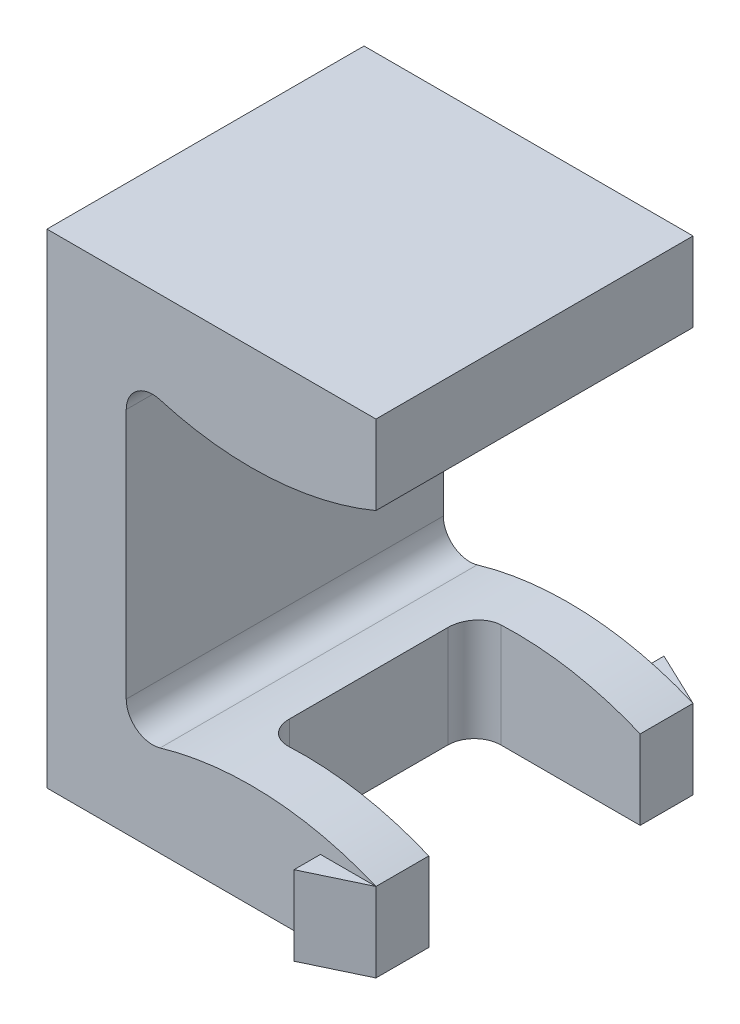
SolidWorks part; units mm, degrees
ref_plane "Front Plane" through (0, 0, 0) normal (0, 0, 1) x (1, 0, 0)
ref_plane "Top Plane" through (0, 0, 0) normal (0, 1, 0) x (1, 0, 0)
ref_plane "Right Plane" through (0, 0, 0) normal (1, 0, 0) x (0, 0, -1)
sketch "Sketch1" plane through (0, 0, 0) normal (0, 0, 1) x (1, 0, 0)
  line L2 (-159.7982, 9.1594) -> (-172.2482, 9.1594)
  line L3 (-172.2482, 9.1594) -> (-172.2482, -9.1594)
  line L7 (-169.2482, -22.8519) -> (-169.2482, 6.1594) construction
  line L12 (-169.2482, 5.1594) -> (-169.2482, 1.9844) construction
  line L13 (-142.8048, 5.1594) -> (-142.8048, -5.1594) construction
  line L15 (-156.5482, 5.1594) -> (21.2518, 5.1594) construction
  line L16 (-156.5482, -5.1594) -> (21.2518, -5.1594) construction
  line L23 (-159.7982, 6.1594) -> (-159.7982, 9.1594)
  line L28 (-164.5232, 5.2094) -> (-144.5007, 5.2094) construction
  line L29 (-156.5482, 5.1594) -> (-169.2482, 5.1594) construction
  line L30 (-169.2482, 6.1594) -> (-169.2482, 5.1594)
  line L34 (-169.2482, 5.1594) -> (-169.2482, -5.1594)
  line L35 (-172.2482, 0) -> (-169.2482, 0) construction
  line L36 (-169.2482, -6.1594) -> (-169.2482, -5.1594)
  line L37 (-159.7982, -6.1594) -> (-159.7982, -9.1594)
  line L38 (-159.7982, -9.1594) -> (-172.2482, -9.1594)
  line L39 (-159.7982, 5.1594) -> (-159.7982, 1.9844) construction
  arc A5 (-169.2482, 6.1594) -> (-159.7982, 6.1594) centre (-164.5232, 17.4347) ccw
  arc A6 (-169.2482, -6.1594) -> (-159.7982, -6.1594) centre (-164.5232, -17.4347) cw
  point P30 (-142.8048, 0)
  dimension "D4" = 3
  dimension "D3" = 3
  dimension "D1" = 0.05
  dimension "D2" = 1
extrude "MainBody" add sketch "Sketch1" along normal mid plane 12
sketch "Sketch3" plane through (0, -9.1594, 0) normal (0, -1, 0) x (1, 0, 0)
  line L0 (-159.7982, -6) -> (-161.8982, -7)
  line L1 (-161.8982, -7) -> (-161.8982, -6)
  line L2 (-172.2482, -6) -> (-159.7982, -6) construction
  line L3 (-161.8982, -6) -> (-159.7982, -6)
  line L4 (-162.8982, -12.7) -> (-162.8982, -6.35) construction
  line L5 (7.9475, 0) -> (-7.9475, 0) construction
  line L6 (-161.8982, 6) -> (-159.7982, 6)
  line L7 (-161.8982, 7) -> (-161.8982, 6)
  line L8 (-159.7982, 6) -> (-161.8982, 7)
  dimension "D1" = 1
  dimension "D2" = 1
extrude "Hook" add sketch "Sketch3" against normal up to vertex (3 mm away) up to point (-159.7982, -6.1594, -6)
sketch "Sketch4" plane through (0, -9.1594, 0) normal (0, -1, 0) x (1, 0, 0)
  line L0 (-159.7982, 6) -> (-159.7982, -6) construction
  line L1 (-159.7982, 4) -> (-166.0732, 4)
  line L2 (-159.7982, 4) -> (-159.7982, -4)
  line L3 (-159.7982, -4) -> (-166.0732, -4)
  line L4 (-166.0732, 4) -> (-166.0732, -4)
  line L5 (-172.2482, 6) -> (-172.2482, -6) construction
  line L6 (-172.2482, -6) -> (-161.8982, -6) construction
  line L7 (-162.8982, -6.35) -> (-169.2482, -6.35) construction
  point P6 (-166.0732, 0)
  point P9 (-172.2482, 0)
  point P14 (-166.0732, -6.35)
  dimension "D1" = 2
extrude "Flex" cut sketch "Sketch4" against normal up to next
fillet "Fillet1" radius 1 2 edges at (-166.0732, -7.2337, -4) (-166.0732, -7.2337, 4)
fillet "Fillet2" radius 1 2 edges at (-169.2482, 6.1594, 0) (-169.2482, -6.1594, 0)
equation "\"HookThickness\"= 3mm"
equation "\"D3@Sketch1\"=\"HookThickness\""
equation "\"D4@Sketch1\"=\"HookThickness\""
